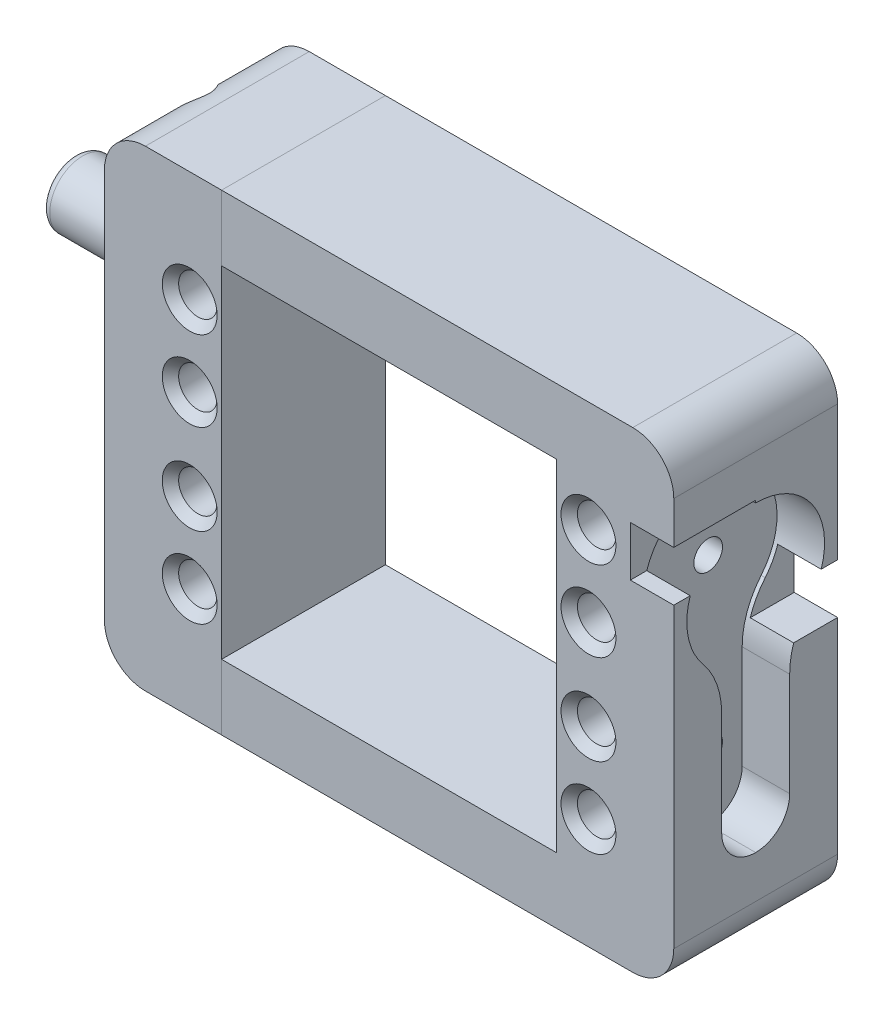
SolidWorks part; units mm, degrees
material "ABS"
ref_plane "Front Plane" through (0, 0, 0) normal (0, 0, 1) x (1, 0, 0)
ref_plane "Top Plane" through (0, 0, 0) normal (0, 1, 0) x (1, 0, 0)
ref_plane "Right Plane" through (0, 0, 0) normal (1, 0, 0) x (0, 0, -1)
sketch "Sketch1" plane through (0, 0, 0) normal (1, 0, 0) x (0, 0, -1)
  line L1 (-10, 10) -> (10, 10)
  line L2 (-10, 10) -> (-10, -10)
  line L3 (-10, -10) -> (10, -10)
  line L4 (10, 10) -> (10, -10)
  line L5 (-10, 10) -> (10, -10) construction
  line L6 (-10, -10) -> (10, 10) construction
  point P0 (0, 0)
  dimension "D1" = 20
  dimension "D2" = 20
extrude "Boss-Extrude1" add sketch "Sketch1" along normal blind 20
sketch "Sketch2" plane through (20, 0, 0) normal (1, 0, 0) x (0, 0, -1)
  line L1 (-10, 35) -> (10, 35)
  line L2 (-10, 35) -> (-10, -35)
  line L3 (-10, -35) -> (10, -35)
  line L4 (10, 35) -> (10, -35)
  line L5 (-10, 35) -> (10, -35) construction
  line L6 (-10, -35) -> (10, 35) construction
  point P0 (0, 0)
  dimension "D1" = 20
  dimension "D2" = 70
extrude "Boss-Extrude2" add sketch "Sketch2" along normal blind 10.3
sketch "Sketch4" plane through (30.3, 0, 0) normal (1, 0, 0) x (0, 0, -1)
  line L0 (0, 7.65) -> (0, 8.1702) construction
  line L1 (7.65, 7.65) -> (-7.65, 7.65) construction
  line L17 (4.15, -26.55) -> (-4.15, -26.55) construction
  line L18 (-7.65, 7.65) -> (7.65, 7.65) construction
  line L22 (-7.65, 7.65) -> (-7.65, -27.55) construction
  line L23 (-7.65, -27.55) -> (7.65, -27.55) construction
  line L24 (7.65, 7.65) -> (7.65, -27.55) construction
  line L25 (-7.65, 7.65) -> (7.65, -27.55) construction
  line L26 (-7.65, -27.55) -> (7.65, 7.65) construction
  line L27 (4.15, -26.55) -> (4.15, -28.55) construction
  line L28 (4.15, -28.55) -> (-4.15, -28.55) construction
  line L29 (-4.15, -26.55) -> (-4.15, -28.55) construction
  line L30 (4.15, -26.55) -> (-4.15, -28.55) construction
  line L31 (4.15, -28.55) -> (-4.15, -26.55) construction
  line L34 (4.15, -28.55) -> (-4.15, -28.55)
  line L35 (-4.15, -28.55) -> (-4.15, -7.3118)
  line L36 (4.15, -28.55) -> (4.15, -7.3118)
  arc A1 (4.15, -6.4265) -> (-4.15, -6.4265) centre (0, 0) ccw construction
  arc A2 (4.15, -7.3118) -> (-4.15, -7.3118) centre (0, 0) ccw
  point P1 (0, -27.55)
  point P7 (0, -13.75)
  point P10 (0, 7.65)
  point P14 (0, -9.95)
  dimension "D1" = 15.3
  dimension "D5" = 2
  dimension "D2" = 15.3
  dimension "D3" = 35.2
  dimension "D4" = 8.3
extrude "Cut-Extrude1" cut sketch "Sketch4" against normal blind 5.8
fillet "Fillet1" radius 4.15 2 edges at (27.4, -28.55, 4.15) (27.4, -28.55, -4.15)
fillet "Fillet2" radius 10 2 edges at (27.4, -7.3118, 4.15) (27.4, -7.3118, -4.15)
sketch "Sketch5" plane through (0, 0, 0) normal (-1, 0, 0) x (0, 0, 1)
  circle A0 centre (0, 0) radius 1.75
  dimension "D1" = 3.5
extrude "Cut-Extrude2" cut sketch "Sketch5" against normal through all
sketch "Sketch6" plane through (24.5, 0, 0) normal (1, 0, 0) x (0, 0, -1)
  line L0 (0, -19.35) -> (0, 0) construction
  line L1 (0, -25.65) -> (0, -23.15) construction
  line L2 (0, -23.15) -> (0, -21.85) construction
  line L3 (0, -21.85) -> (0, -19.35) construction
  line L5 (0, 0) -> (1.164, 0) construction
  line L6 (0, 0) -> (0, -9.35) construction
  line L7 (0, -9.35) -> (1.164, -9.35) construction
  line L8 (1.164, 0) -> (1.164, -9.35) construction
  line L9 (0, 0) -> (1.164, -9.35) construction
  line L10 (0, -9.35) -> (1.164, 0) construction
  circle A0 centre (0, -20.6) radius 1.75
  circle A1 centre (0, -9.35) radius 1.75 construction
  point P11 (0.582, -4.675)
  dimension "D5" = 3.5
  dimension "D6" = 9.35
  dimension "D7" = 3.5
  dimension "D1" = 19.35
  dimension "D2" = 2.5
  dimension "D3" = 1.3
  dimension "D4" = 2.5
extrude "Cut-Extrude3" cut sketch "Sketch6" against normal up to next
sketch "Sketch13" plane through (0, 0, 0) normal (-1, 0, 0) x (0, 0, 1)
  line L1 (-10, 10) -> (10, 10)
  line L2 (-10, 10) -> (-10, -10)
  line L3 (-10, -10) -> (10, -10)
  line L4 (10, 10) -> (10, -10)
extrude "Cut-Extrude9" cut sketch "Sketch13" against normal up to surface (20 mm away) up to face at (20, 22.5, 0)
sketch "Sketch29" plane through (30.3, 0, 0) normal (1, 0, 0) x (0, 0, -1)
  line L0 (0, 0) -> (0, 2.6) construction
  line L1 (15.1094, -8.7) -> (15.1094, -2.6)
  line L2 (0, 2.6) -> (-15.1094, 2.6)
  line L4 (0, 2.6) -> (0, 3.8)
  line L5 (0, 3.8) -> (0, 7.5)
  line L6 (0, 7.5) -> (0, 8.7)
  line L7 (0, 8.7) -> (-15.1094, 8.7)
  line L8 (-15.1094, 8.7) -> (-15.1094, 2.6)
  line L9 (0, -2.6) -> (15.1094, -2.6)
  line L10 (0, -2.6) -> (0, -3.8)
  line L11 (0, -3.8) -> (0, -7.5)
  line L12 (0, -7.5) -> (0, -8.7)
  line L13 (0, -8.7) -> (15.1094, -8.7)
  point P19 (0, 0)
  dimension "D1" = 2.6
  dimension "D2" = 1.2
  dimension "D3" = 3.7
  dimension "D4" = 1.2
  dimension "D5" = 2
extrude "Cut-Extrude18" cut sketch "Sketch29" against normal blind 5.3
sketch "Sketch32" plane through (30.3, 0, 0) normal (1, 0, 0) x (0, 0, -1)
  line L0 (0, -28.55) -> (0, -38.725) construction
  line L1 (10, -35) -> (10, -8.7) construction
  line L2 (-10, -35) -> (10, -35)
  line L3 (-10, -35) -> (-10, -38.725)
  line L4 (-10, -38.725) -> (10, -38.725)
  line L5 (10, -35) -> (10, -38.725)
  dimension "D1" = 10.175
extrude "Boss-Extrude3" add sketch "Sketch32" against normal up to surface (10.3 mm away) up to face at (20, 0, 0)
sketch "Sketch31" plane through (30.3, 0, 0) normal (1, 0, 0) x (0, 0, -1)
  line L2 (0, 8.7) -> (0, 18.875) construction
  line L3 (10, -2.6) -> (10, 35) construction
  line L4 (-10, 35) -> (10, 35)
  line L5 (-10, 35) -> (-10, 18.875)
  line L6 (-10, 18.875) -> (10, 18.875)
  line L7 (10, 35) -> (10, 18.875)
  dimension "D1" = 10.175
extrude "Cut-Extrude19" cut sketch "Sketch31" against normal through all
sketch "Sketch34" plane through (20, 0, 0) normal (-1, 0, 0) x (0, 0, 1)
  line L4 (10, -38.725) -> (10, 18.875)
  line L5 (10, 18.875) -> (-10, 18.875)
  line L6 (-10, 18.875) -> (-10, -38.725)
  line L7 (-10, -38.725) -> (10, -38.725)
  line L8 (10, -38.725) -> (10, 18.875)
  line L9 (10, 18.875) -> (-10, 18.875)
  line L10 (-10, 18.875) -> (-10, -38.725)
  line L11 (-10, -38.725) -> (10, -38.725)
  circle A0 centre (0, -20.6) radius 1.75 construction
  circle A1 centre (0, 0) radius 1.75 construction
  circle A2 centre (0, -20.6) radius 1.75
  circle A3 centre (0, 0) radius 1.75
  dimension "D1" = 0
extrude "Boss-Extrude5" add sketch "Sketch34" along normal blind 4
sketch "Sketch35" plane through (16, 0, 0) normal (-1, 0, 0) x (0, 0, 1)
  line L0 (10, -38.725) -> (10, 18.875) construction
  line L1 (-10, 18.875) -> (10, 18.875)
  line L2 (-10, 18.875) -> (-10, 10.875)
  line L3 (-10, 10.875) -> (10, 10.875)
  line L4 (10, 18.875) -> (10, 10.875)
  line L5 (0, 10.875) -> (0, -30.725) construction
  line L6 (-10, -38.725) -> (10, -38.725)
  line L7 (-10, -38.725) -> (-10, -30.725)
  line L8 (-10, -30.725) -> (10, -30.725)
  line L9 (10, -38.725) -> (10, -30.725)
  dimension "D1" = 41.6
extrude "Boss-Extrude6" add sketch "Sketch35" along normal blind 40.9
sketch "Sketch37" plane through (-24.9, 0, 0) normal (-1, 0, 0) x (0, 0, 1)
  line L1 (-10, 18.875) -> (10, 18.875)
  line L2 (-10, 18.875) -> (-10, -38.725)
  line L3 (-10, -38.725) -> (10, -38.725)
  line L4 (10, 18.875) -> (10, -38.725)
extrude "Boss-Extrude7" add sketch "Sketch37" along normal blind 14.3
sketch "Sketch38" plane through (0, 0, 10) normal (0, 0, 1) x (1, 0, 0)
  line L0 (-24.9, 10.875) -> (-24.9, -9.925) construction
  line L1 (-24.9, -9.925) -> (-24.9, -30.725) construction
  line L2 (-24.9, -30.725) -> (-24.9, 10.875) construction
  line L3 (-24.9, -9.925) -> (-39.2, -9.925) construction
  line L4 (-39.2, -38.725) -> (-39.2, 18.875) construction
  line L5 (-24.9, 0.475) -> (-28.79, 0.475) construction
  line L6 (-28.79, 0.475) -> (-28.79, 5.375) construction
  line L7 (-24.9, 10.875) -> (16, 10.875) construction
  line L8 (-4.45, 10.875) -> (-4.45, -38.725) construction
  line L9 (-39.2, -38.725) -> (30.3, -38.725) construction
  circle A0 centre (-28.79, 5.375) radius 2.35
  circle A1 centre (-28.79, -4.425) radius 2.35
  circle A2 centre (-28.79, -25.225) radius 2.35
  circle A3 centre (-28.79, -15.425) radius 2.35
  circle A4 centre (19.89, 5.375) radius 2.35
  circle A5 centre (19.89, -4.425) radius 2.35
  circle A6 centre (19.89, -15.425) radius 2.35
  circle A7 centre (19.89, -25.225) radius 2.35
  dimension "D4" = 4.7
  dimension "D1" = 41.6
  dimension "D2" = 3.89
  dimension "D3" = 4.9
extrude "Cut-Extrude20" cut sketch "Sketch38" against normal blind 8
chamfer "Chamfer1" distance 1 angle 45 8 edges at (22.24, -25.225, 10) (17.54, -15.425, 10) (22.24, -4.425, 10) (17.54, 5.375, 10) (-26.44, 5.375, 10) (-26.44, -15.425, 10) (-31.14, -25.225, 10) (-31.14, -4.425, 10)
sketch "Sketch41" plane through (16, 0, 0) normal (-1, 0, 0) x (0, 0, 1)
  circle A0 centre (0, 0) radius 3.5
  circle A1 centre (0, -20.6) radius 3.5
  dimension "D1" = 7
  dimension "D2" = 7
extrude "Cut-Extrude23" cut sketch "Sketch41" against normal blind 4
sketch "Sketch42" plane through (-39.2, 0, 0) normal (-1, 0, 0) x (0, 0, 1)
  line L0 (10, -38.725) -> (10, 18.875) construction
  line L1 (-10, -38.725) -> (10, -38.725) construction
  line L2 (-10, -38.725) -> (-10, -30.725) construction
  line L3 (-10, -30.725) -> (10, -30.725) construction
  line L4 (10, -38.725) -> (10, -30.725) construction
  line L5 (-10, -9.925) -> (10, -9.925) construction
  line L6 (-10, 18.875) -> (-10, -38.725) construction
  circle A0 centre (0, -34.725) radius 1.75
  circle A1 centre (0, 14.875) radius 1.75
  point P9 (-10, -34.725)
  dimension "D2" = 3.5
  dimension "D1" = 8
  dimension "D3" = 4
  dimension "D4" = 10
extrude "Cut-Extrude24" cut sketch "Sketch42" against normal blind 22.3
sketch "Sketch43" plane through (-39.2, 0, 0) normal (-1, 0, 0) x (0, 0, 1)
  circle A0 centre (0, 14.875) radius 3.5
  circle A1 centre (0, -34.725) radius 3.5
  dimension "D1" = 7
  dimension "D2" = 7
extrude "Cut-Extrude25" cut sketch "Sketch43" against normal blind 11
fillet "Fillet3" radius 5 4 edges at (-39.2, -38.725, 0) (30.3, -38.725, 0) (30.3, 18.875, 0) (-39.2, 18.875, 0)
sketch "Sketch44" plane through (0, 0, 10) normal (0, 0, 1) x (1, 0, 0)
  line L0 (-24.9, 18.875) -> (-24.9, -38.725)
  line L1 (-34.2, 18.875) -> (25.3, 18.875) construction
  line L2 (-34.2, -38.725) -> (25.3, -38.725) construction
split "Split1" trim tools "Sketch44" bodies to split 171 resulting bodies 172 173
sketch "Sketch45" plane through (-24.9, 0, 0) normal (-1, 0, 0) x (0, 0, 1)
  circle A0 centre (0, 14.875) radius 2.35
  circle A1 centre (0, -34.725) radius 2.35
  dimension "D1" = 4.7
  dimension "D2" = 4.7
extrude "Cut-Extrude26" cut sketch "Sketch45" against normal blind 8
chamfer "Chamfer2" distance 1 angle 45 2 edges at (-24.9, -34.725, 2.35) (-24.9, 14.875, 2.35)
sketch "Sketch46" plane through (-39.2, 0, 0) normal (-1, 0, 0) x (0, 0, 1)
  circle A1 centre (0, 0) radius 4
  dimension "D1" = 8
extrude "Boss-Extrude8" add sketch "Sketch46" along normal blind 13.67
fillet "Fillet4" radius 4 1 edges at (-39.2, 0, 4)
fillet "Fillet5" radius 1 1 edges at (-52.87, 0, 4)
mirror "Mirror1" [suppressed] of bodies 177 174 167 172 173
delete or keep bodies "Body-Delete/Keep 1" [suppressed] type delete bodies bodies 177 174
